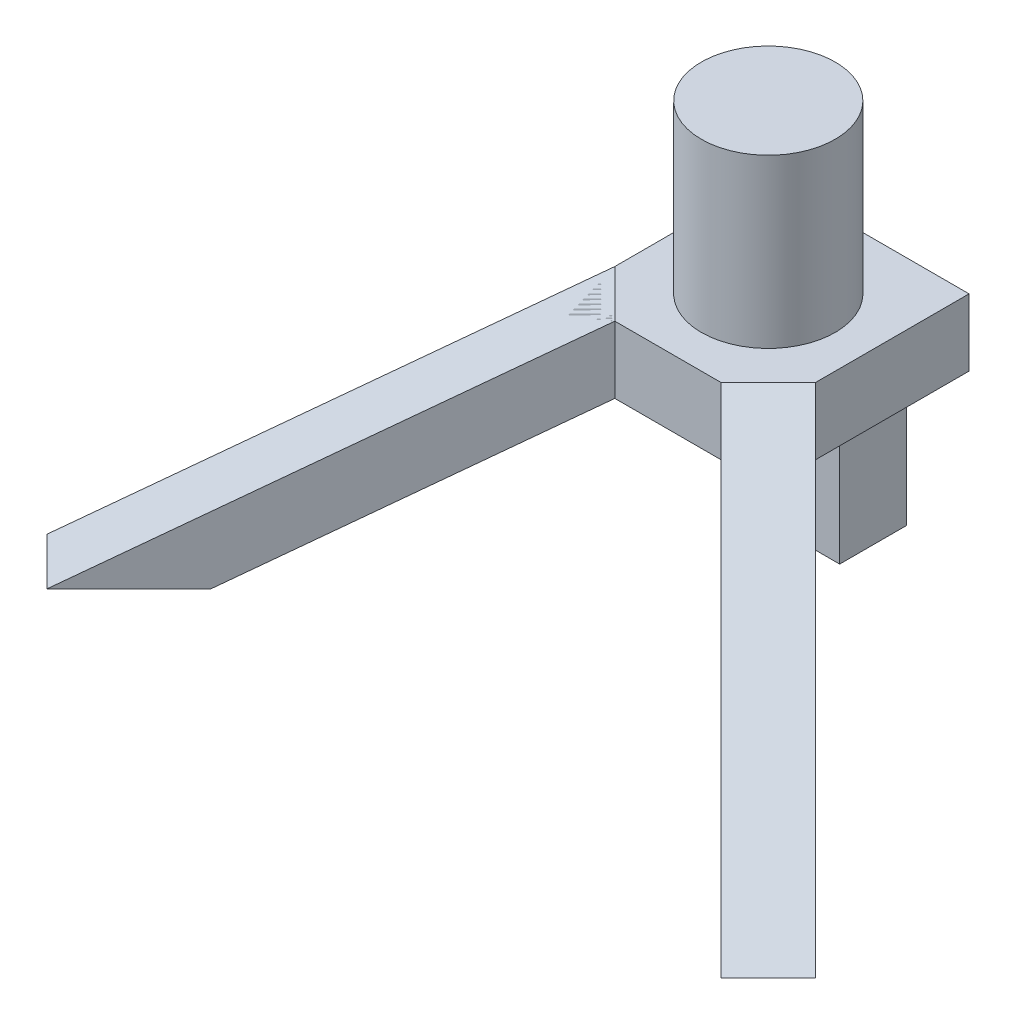
SolidWorks part; units mm, degrees
ref_plane "Front Plane" through (0, 0, 0) normal (0, 0, 1) x (1, 0, 0)
ref_plane "Top Plane" through (0, 0, 0) normal (0, 1, 0) x (1, 0, 0)
ref_plane "Right Plane" through (0, 0, 0) normal (1, 0, 0) x (0, 0, -1)
sketch "Sketch1" plane through (0, 0, 0) normal (0, 1, 0) x (1, 0, 0)
sketch "Sketch2" plane through (0, 0, 0) normal (0, 1, 0) x (1, 0, 0)
  line L0 (-30, -30) -> (30, -30)
  line L1 (-30, -30) -> (-30, 30)
  line L2 (30, -30) -> (30, 30)
  line L3 (-30, 30) -> (30, 30)
  circle A0 centre (0, 0) radius 20
  point P0 (0, 30)
  point P3 (0, 0)
  point P6 (-30, 0)
  point P10 (0, 0)
  point P11 (0, 0)
  point P13 (0, 0)
  point P14 (0, 0)
  point P15 (0, 0)
  dimension "D4" = 40
  dimension "D2" = 60
  dimension "D3" = 60
extrude "Boss-Extrude3" add sketch "Sketch2" along normal blind 20 contours A0 | L3 L1 L0 L2 A0 region at (-29.1515, 0, 0) region at (0, 0, 0)
extrude "Boss-Extrude5" add sketch "Sketch2<4>" along normal blind 50 from surface contours A0 region at (0, 0, 0) starting at face at (0, 20, 0)
sketch "Sketch2<4>" plane through (0, 0, 0) normal (0, 1, 0) x (1, 0, 0) same geometry as "Sketch2"
sketch "Sketch3" plane through (-30, 0, 30) normal (0, -1, 0) x (1, 0, 0)
  line L0 (0, 0) -> (60, -60) construction
  line L1 (60, 0) -> (0, -60) construction
ref_plane "Plane2" through (0, 0, 0) normal (0.7071, 0, 0.7071) x (0.7071, 0, -0.7071)
ref_plane "Plane3" through (0, 0, 0) normal (0.7071, 0, -0.7071) x (-0.7071, 0, -0.7071)
sketch "Sketch5" plane through (0, 0, 0) normal (0.7071, 0, 0.7071) x (0.7071, 0, -0.7071)
  line L0 (-32.4264, 20) -> (-152.4264, -49.282)
  line L1 (-42.4264, 20) -> (-42.4264, 0) construction
  line L2 (-32.4264, 0) -> (-117.7854, -49.282)
  line L3 (-152.4264, -49.282) -> (-117.7854, -49.282)
  line L5 (-32.4264, 20) -> (-32.4264, 0)
  dimension "D1" = 60
  dimension "D2" = 10
  dimension "D3" = 120
extrude "Boss-Extrude6" add sketch "Sketch5" along normal blind 10 and the other way blind 10 separate body contours L2 L3 L0 L5
sketch "Sketch6" plane through (-22.9289, 0, 22.9289) normal (0.7071, 0, -0.7071) x (-0.7071, 0, -0.7071)
  line L4 (10, 20) -> (-10, 20)
  line L5 (-10, 20) -> (-10, 0)
  line L6 (-10, 0) -> (10, 0)
  line L7 (10, 0) -> (10, 20)
  line L8 (10, 20) -> (-10, 20)
  line L9 (-10, 20) -> (-10, 0)
  line L10 (-10, 0) -> (10, 0)
  line L11 (10, 0) -> (10, 20)
  dimension "D1" = 0
sketch "Sketch8" plane through (-11.856, 29.041, 11.856) normal (-0.3536, 0.866, 0.3536) x (0.9259, 0.2704, 0.2637)
  line L4 (-93.1132, -126.3644) -> (-76.2891, -137.1787)
  line L5 (-76.2891, -137.1787) -> (-1.3652, -20.6179)
  line L6 (-1.3652, -20.6179) -> (-18.1893, -9.8036)
  line L7 (-18.1893, -9.8036) -> (-93.1132, -126.3644)
  line L8 (-93.1132, -126.3644) -> (-76.2891, -137.1787)
  line L9 (-76.2891, -137.1787) -> (-1.3652, -20.6179)
  line L10 (-1.3652, -20.6179) -> (-18.1893, -9.8036)
  line L11 (-18.1893, -9.8036) -> (-93.1132, -126.3644)
  dimension "D1" = 0
mirror "Mirror3" about plane through (0, 0, 0) normal (1, 0, 0) of "Boss-Extrude6"
sketch "Sketch11" plane through (11.856, 29.041, 11.856) normal (0.3536, 0.866, 0.3536) x (0.9259, -0.2704, -0.2637)
  line L0 (1.3652, -20.6179) -> (18.1893, -9.8036)
  line L1 (18.1893, -9.8036) -> (18.1893, -28.2976)
  line L2 (19.8672, -30.9078) -> (-19.8672, 30.9078) construction
  line L3 (25.2347, -39.2582) -> (-25.2347, 39.2582) construction
  line L4 (18.1893, -28.2976) -> (1.3652, -20.6179)
extrude "Cut-Extrude2" cut sketch "Sketch11" along normal blind 10 contours L4 L0 L1
sketch "Sketch12" plane through (-11.856, 29.041, 11.856) normal (-0.3536, 0.866, 0.3536) x (0.9259, 0.2704, 0.2637)
  line L4 (-93.1132, -126.3644) -> (-76.2891, -137.1787)
  line L5 (-76.2891, -137.1787) -> (-1.3652, -20.6179)
  line L6 (-1.3652, -20.6179) -> (-18.1893, -9.8036)
  line L7 (-18.1893, -9.8036) -> (-93.1132, -126.3644)
  line L8 (-93.1132, -126.3644) -> (-76.2891, -137.1787)
  line L9 (-76.2891, -137.1787) -> (-1.3652, -20.6179)
  line L10 (-1.3652, -20.6179) -> (-18.1893, -9.8036)
  line L11 (-18.1893, -9.8036) -> (-93.1132, -126.3644)
  dimension "D1" = 0
extrude "Cut-Extrude3" cut sketch "Sketch12" along normal blind 10
sketch "Sketch13" plane through (0, 0, 0) normal (0, -1, 0) x (1, 0, 0)
  line L0 (-30, -30) -> (30, -30) construction
  line L1 (-8.666, -30) -> (11.334, -30)
  line L2 (-8.666, -30) -> (-8.666, -10)
  line L3 (-8.666, -10) -> (11.334, -10)
  line L4 (11.334, -30) -> (11.334, -10)
  dimension "D1" = 20
  dimension "D2" = 20
extrude "Boss-Extrude8" add sketch "Sketch13" along normal up to surface (49.282 mm away) up to face at (95.5343, -49.282, 95.5343)
